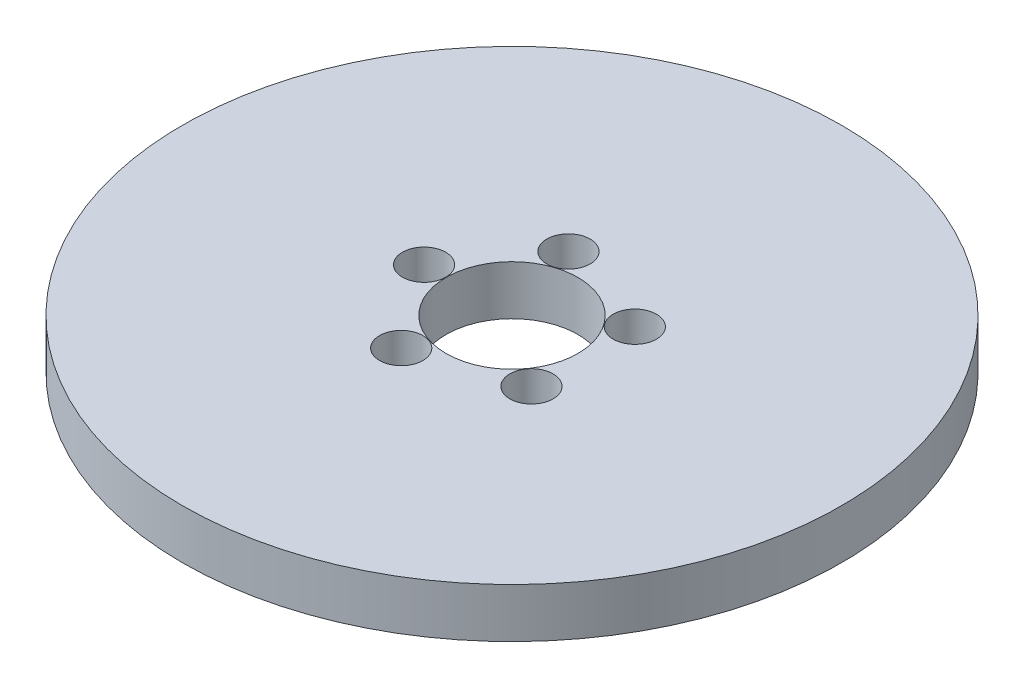
SolidWorks part; units mm, degrees
ref_plane "Front Plane" through (0, 0, 0) normal (0, 0, 1) x (1, 0, 0)
ref_plane "Top Plane" through (0, 0, 0) normal (0, 1, 0) x (1, 0, 0)
ref_plane "Right Plane" through (0, 0, 0) normal (1, 0, 0) x (0, 0, -1)
sketch "Sketch1" plane through (0, 0, 0) normal (0, 1, 0) x (1, 0, 0)
  circle A0 centre (0, 0) radius 100
  dimension "FLANGE_OD" = 200
extrude "Boss-Extrude1" add sketch "Sketch1" along normal blind 15
sketch "Sketch2" plane through (0, 0, 0) normal (0, 1, 0) x (1, 0, 0)
  circle A0 centre (0, 0) radius 20
  dimension "BORE_D" = 40
extrude "Cut-Extrude1" cut sketch "Sketch2" along normal through all
sketch "Sketch3" plane through (0, 15, 0) normal (0, 1, 0) x (1, 0, 0)
  circle A0 centre (0, 0) radius 26.6779 construction
  circle A1 centre (-26.6779, 0) radius 6.5716
  dimension "BOLT_D" = 13.1431
  dimension "BOLT_PCD" = 53.3558
extrude "Cut-Extrude2" cut sketch "Sketch3" against normal blind 13.9177
pattern_circular "CirPattern1" count 5 over 360 about axis through (0, 0, 0) along (0, 1, 0) of "Cut-Extrude2"
